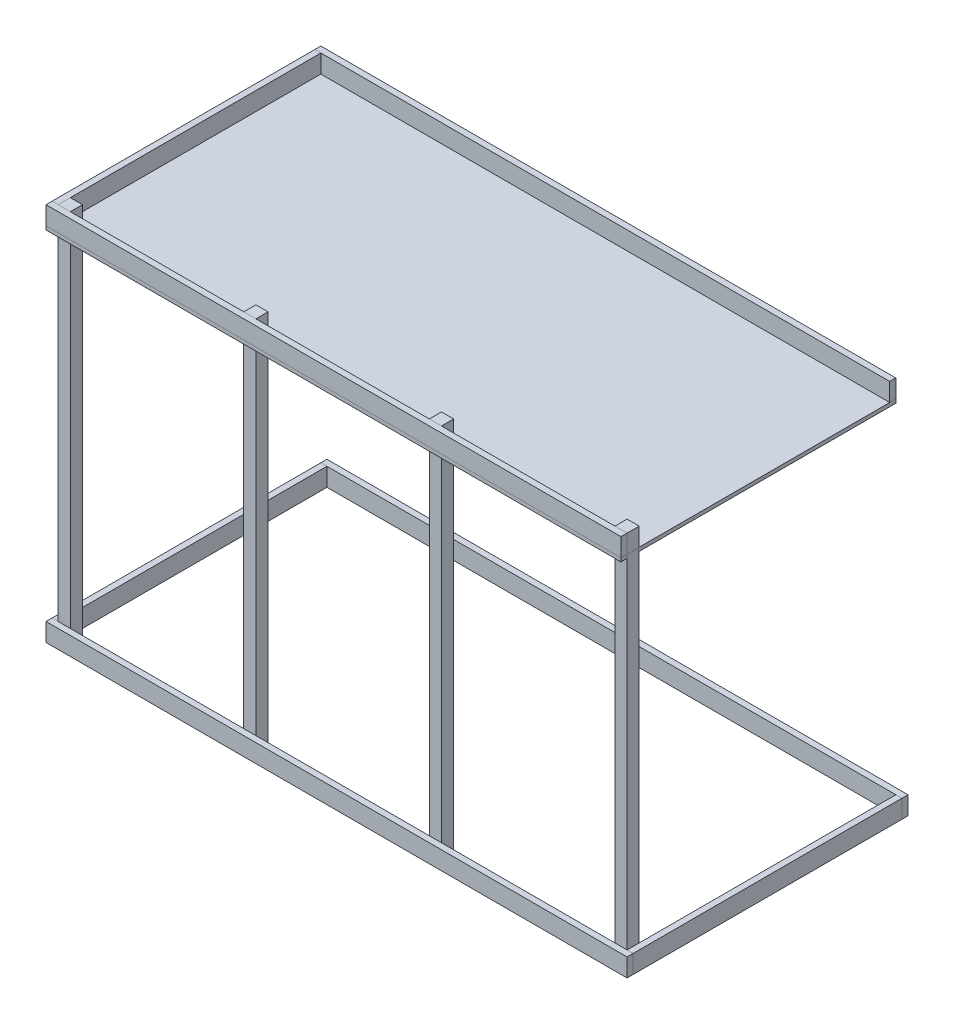
SolidWorks part; units mm, degrees
note: The reader was unsure of these and kept them because the rebuilt part matched: shared geometry of "Эскиз1<3>".
ref_plane "Спереди" through (0, 0, 0) normal (0, 0, 1) x (1, 0, 0)
ref_plane "Сверху" through (0, 0, 0) normal (0, 1, 0) x (1, 0, 0)
ref_plane "Справа" through (0, 0, 0) normal (1, 0, 0) x (0, 0, -1)
sketch "Эскиз1" plane through (0, 0, 0) normal (0, 0, 1) x (1, 0, 0)
  line L0 (-8127, 200) -> (-8127, 0) construction
  line L1 (-3399, 200) -> (-8127, 200)
  line L2 (-3399, 200) -> (-3399, 50)
  line L3 (-3399, 50) -> (-8127, 50)
  line L4 (-8127, 200) -> (-8127, 50)
  dimension "D1" = 150
extrude "Бобышка-Вытянуть1" add sketch "Эскиз1" along normal blind 50 contours L1 L4 L3 L2
extrude "Бобышка-Вытянуть2" add sketch "Эскиз1<3>" against normal blind 50 from surface separate body
sketch "Эскиз1<3>" plane through (0, 0, 0) normal (0, 0, 1) x (1, 0, 0) same geometry as "Эскиз1"
sketch "Эскиз2" plane through (0, 200, 0) normal (0, 1, 0) x (1, 0, 0)
  line L0 (-3399, -2210) -> (-8127, -2210) construction
  line L1 (-3399, -2210) -> (-3499, -2210)
  line L2 (-3399, -2210) -> (-3399, -2110)
  line L3 (-3399, -2110) -> (-3499, -2110)
  line L4 (-3499, -2210) -> (-3499, -2110)
  line L5 (-8077, -2210) -> (-7977, -2210)
  line L6 (-8077, -2210) -> (-8077, -2110)
  line L7 (-8077, -2110) -> (-7977, -2110)
  line L8 (-7977, -2210) -> (-7977, -2110)
  line L9 (-8127, -2210) -> (-8127, -2260) construction
  line L10 (-6551, -2210) -> (-6451, -2210)
  line L11 (-6551, -2210) -> (-6551, -2110)
  line L12 (-6551, -2110) -> (-6451, -2110)
  line L13 (-6451, -2210) -> (-6451, -2110)
  line L14 (-5025, -2210) -> (-4925, -2210)
  line L15 (-5025, -2210) -> (-5025, -2110)
  line L16 (-5025, -2110) -> (-4925, -2110)
  line L17 (-4925, -2210) -> (-4925, -2110)
  line L18 (-3499, -2110) -> (-4925, -2110) construction
  line L19 (-5025, -2110) -> (-6451, -2110) construction
  line L20 (-6551, -2110) -> (-7977, -2110) construction
  dimension "D1" = 100
  dimension "D2" = 50
  dimension "D3" = 1426
extrude "Бобышка-Вытянуть3" add sketch "Эскиз2" against normal up to surface (3118 mm away) separate body
sketch "Эскиз3" plane through (0, 0, 2210) normal (0, 0, 1) x (1, 0, 0)
  line L0 (-3399, -2918) -> (-3499, -2918) construction
  line L1 (-3349, -2918) -> (-8127, -2918)
  line L2 (-3349, -2918) -> (-3349, -2768)
  line L3 (-3349, -2768) -> (-8127, -2768)
  line L4 (-8127, -2918) -> (-8127, -2768)
  line L5 (-3349, -2918) -> (-3349, -2768) construction
  line L6 (-8127, 50) -> (-8127, 200) construction
  dimension "D1" = 150
extrude "Бобышка-Вытянуть4" add sketch "Эскиз3" along normal blind 50 separate body
sketch "Эскиз4" plane through (-8127, 0, 0) normal (-1, 0, 0) x (0, 0, 1)
  line L0 (0, 200) -> (0, 0) construction
  line L1 (2210, -2918) -> (0, -2918)
  line L2 (2210, -2918) -> (2210, -2768)
  line L3 (2210, -2768) -> (0, -2768)
  line L4 (0, -2918) -> (0, -2768)
  line L6 (2210, 50) -> (50, 50)
  line L7 (2210, 50) -> (2210, 200)
  line L8 (2210, 200) -> (50, 200)
  line L9 (50, 50) -> (50, 200)
extrude "Бобышка-Вытянуть5" add sketch "Эскиз4" against normal blind 50 separate body
sketch "Эскиз5" plane through (0, 0, 0) normal (0, 0, -1) x (-1, 0, 0)
  line L0 (3349, -2918) -> (3349, -2768) construction
  line L1 (8127, -2918) -> (3349, -2918)
  line L2 (8127, -2918) -> (8127, -2768)
  line L3 (8127, -2768) -> (3349, -2768)
  line L4 (3349, -2918) -> (3349, -2768)
  line L5 (8127, -2768) -> (8127, -2918) construction
  point P7 (8127, -2768)
  point P10 (8127, -2815.2075)
extrude "Бобышка-Вытянуть6" add sketch "Эскиз5" along normal blind 50 separate body
sketch "Эскиз6" plane through (-3399, 0, 0) normal (1, 0, 0) x (0, 0, -1)
  line L1 (-2210, -2918) -> (0, -2918)
  line L2 (-2210, -2918) -> (-2210, -2768)
  line L3 (-2210, -2768) -> (0, -2768)
  line L4 (0, -2918) -> (0, -2768)
  point P5 (0, 0)
  point P7 (0, 0)
extrude "Бобышка-Вытянуть7" add sketch "Эскиз6" along normal blind 50 separate body
sketch "Эскиз7" plane through (0, 50, 0) normal (0, -1, 0) x (1, 0, 0)
  line L1 (-8127, 0) -> (-3399, 0)
  line L2 (-8127, 0) -> (-8127, 2260)
  line L3 (-8127, 2260) -> (-3399, 2260)
  line L4 (-3399, 0) -> (-3399, 2260)
extrude "Бобышка-Вытянуть8" add sketch "Эскиз7" along normal blind 30 separate body
